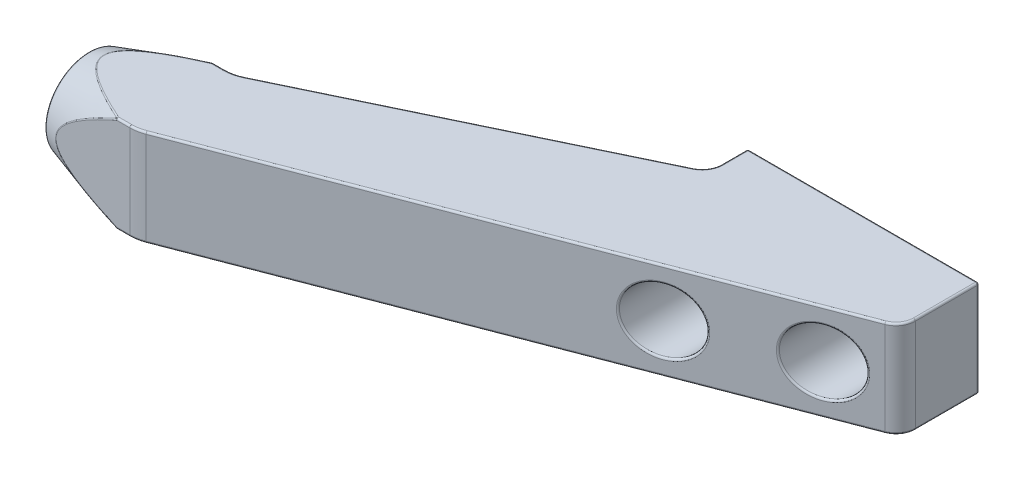
SolidWorks part; units mm, degrees
material "1060 Alloy"
ref_plane "Front Plane" through (0, 0, 0) normal (0, 0, 1) x (1, 0, 0)
ref_plane "Top Plane" through (0, 0, 0) normal (0, 1, 0) x (1, 0, 0)
ref_plane "Right Plane" through (0, 0, 0) normal (1, 0, 0) x (0, 0, -1)
sketch "Sketch1" plane through (0, 0, 0) normal (0, 1, 0) x (1, 0, 0)
  line L0 (-6, 0) -> (6, 0)
  line L1 (6, 0) -> (6, -4)
  line L2 (6, -4) -> (-22.7, -15)
  line L3 (-22.7, -15) -> (-27.7, -15)
  line L4 (-27.7, -15) -> (-27.7, -10)
  line L5 (-27.7, -10) -> (-22.7, -10)
  line L6 (-22.7, -10) -> (-6, -2)
  line L7 (-6, -2) -> (-6, 0)
  point P2 (0, 0)
  dimension "D1" = 12
  dimension "D2" = 4
  dimension "D3" = 2
  dimension "D4" = 27.7
  dimension "D5" = 10
  dimension "D6" = 5
  dimension "D7" = 5
extrude "Boss-Extrude1" add sketch "Sketch1" along normal mid plane 5
fillet "Fillet1" radius 1 2 edges at (-6, 0, 2) (6, 0, 4)
fillet "Fillet2" radius 2 2 edges at (-22.7, 0, 15) (-22.7, 0, 10)
sketch "Sketch2" plane through (0, 0, 0) normal (0, 0, -1) x (-1, 0, 0)
  line L0 (6, 0) -> (-6, 0) construction
  line L1 (6, -2.5) -> (6, 2.5) construction
  line L2 (-6, 2.5) -> (-6, -2.5) construction
  line L3 (0, 0) -> (0, -3.0931) construction
  circle A0 centre (-3, 0) radius 0.875
  circle A1 centre (3, 0) radius 0.875
  dimension "D1" = 1.75
  dimension "D2" = 6
extrude "Cut-Extrude1" cut sketch "Sketch2" against normal blind 15
sketch "Sketch3" plane through (0, 0, 0) normal (0, 0, -1) x (-1, 0, 0)
  circle A0 centre (3, 0) radius 1.65
  circle A1 centre (-3, 0) radius 1.65
  dimension "D1" = 3.3
extrude "Cut-Extrude2" cut sketch "Sketch3" against normal blind 15 from offset 2 offset against normal yes
sketch "Sketch4" plane through (-27.7, 0, 0) normal (-1, 0, 0) x (0, 0, 1)
  line L0 (15, 0) -> (10, 0) construction
  line L1 (15, 2.5) -> (15, -2.5) construction
  line L2 (10, 2.5) -> (10, -2.5) construction
  circle A0 centre (12.5, 0) radius 1
  dimension "D1" = 2
extrude "Cut-Extrude3" cut sketch "Sketch4" against normal blind 4
ref_plane "Plane1" through (0, 0, 12.5) normal (0, 0, 1) x (1, 0, 0)
sketch "Sketch5" plane through (0, 0, 12.5) normal (0, 0, 1) x (1, 0, 0)
  line L0 (-27.7, 0) -> (-30.7314, 0) construction
  line L1 (-27.7, 2.5) -> (-27.7, -2.5) construction
  line L2 (-27.7, 2.25) -> (-27.7, 3.75)
  line L3 (-27.7, 3.75) -> (-22.95, 3.75)
  line L4 (-22.95, 3.75) -> (-27.7, 2.25)
  dimension "D1" = 2.25
  dimension "D2" = 1.5
  dimension "D3" = 4.75
revolve "Cut-Revolve1" cut sketch "Sketch5" angle 360 about L0
fillet "Fillet3" radius 0.1 39 edges at (4.65, 0, 4.5174) (-1.35, 0, 6.8171) (-8.4982, -2.5, 9.5568) (-8.4982, 2.5, 9.5568) (-27.7, 0, 10.25) (-27.7, 0, 13.5) (-26.8743, 0.2322, 15) (-26.9083, -0.005, 10) (-26.9037, 2.5, 12.414) (-23.7, 0, 13.5) (1.35, 0, 2) (-4.65, 0, 2) (2.125, 0, 2) (-3.875, 0, 2) (-2.125, 0, 0) (2.125, 0, 0) (-6, -2.5, 0.6851) (-14.4291, -2.5, 6.0379) (-23.3917, -2.5, 10) (-23.3496, -2.5, 15) (6, -2.5, 1.6562) (0, -2.5, 0) (-6, 2.5, 0.6851) (-23.3917, 2.5, 10) (-23.3496, 2.5, 15) (6, 2.5, 1.6562) (0, 2.5, 0) (-6, 0, 0) (6, 0, 0) (5.824, -2.5, 3.879) (5.824, 2.5, 3.879) (-6.1538, -2.5, 1.9031) (-6.1538, 2.5, 1.9031) (-22.7062, -2.5, 14.9666) (-22.7062, 2.5, 14.9666) (-22.7113, -2.5, 9.9503) (-22.7113, 2.5, 9.9503) (-26.9037, -2.5, 12.414) (-14.4291, 2.5, 6.0379)
